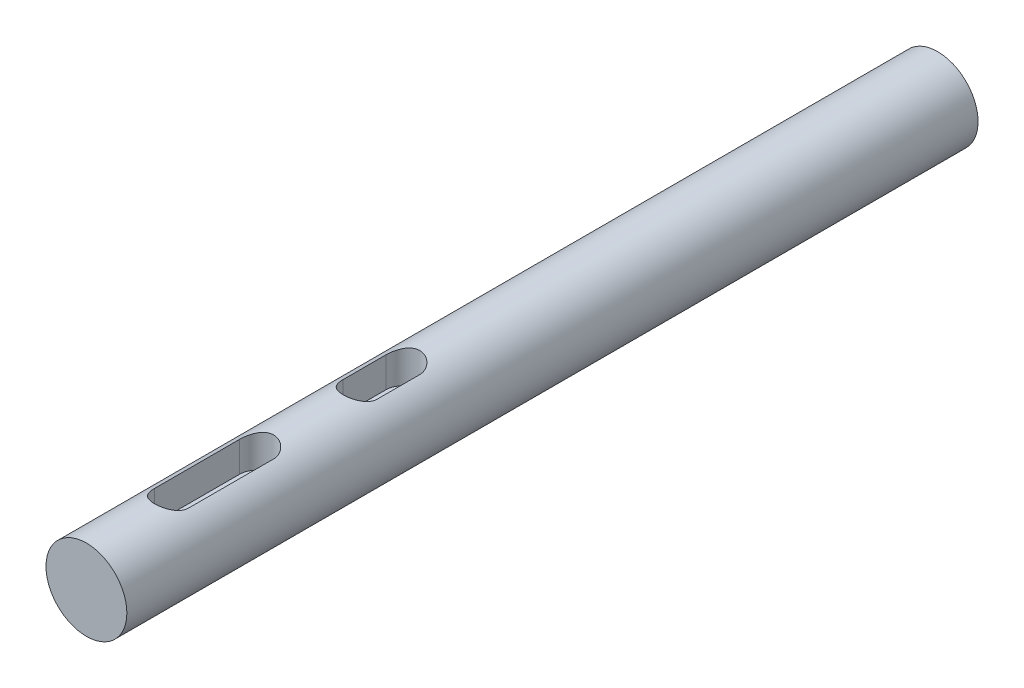
SolidWorks part; units mm, degrees
ref_plane "Front Plane" through (0, 0, 0) normal (0, 0, 1) x (1, 0, 0)
ref_plane "Top Plane" through (0, 0, 0) normal (0, 1, 0) x (1, 0, 0)
ref_plane "Right Plane" through (0, 0, 0) normal (1, 0, 0) x (0, 0, -1)
sketch "Sketch1" plane through (0, 0, 0) normal (0, 0, 1) x (1, 0, 0)
  circle A0 centre (0, 0) radius 4.75
  dimension "D1" = 9.5
extrude "Boss-Extrude1" add sketch "Sketch1" along normal blind 0.0001
sketch "Sketch4" plane through (0, 0, 0) normal (0, 0, -1) x (-1, 0, 0)
  circle A0 centre (0, 0) radius 4.75
  dimension "D1" = 9.5
extrude "Boss-Extrude2" add sketch "Sketch4" along normal blind 105
ref_axis "Axis1" through (0, 0, -105) along (0, 0, 1)
ref_plane "Plane1" through (0, 4.75, 0) normal (0, 1, 0) x (1, 0, 0)
sketch "Sketch5" plane through (0, 4.75, 0) normal (0, 1, 0) x (1, 0, 0)
  line L0 (0, -4.3175) -> (0, 99.6122) construction
  line L1 (0, 10) -> (0, 20) construction
  line L2 (-2, 10) -> (-2, 20)
  line L3 (2, 10) -> (2, 20)
  line L11 (0, 32.17) -> (0, 37.17) construction
  line L12 (-2, 32.17) -> (-2, 37.17)
  line L13 (2, 32.17) -> (2, 37.17)
  arc A0 (-2, 10) -> (2, 10) centre (0, 10) ccw
  arc A1 (2, 20) -> (-2, 20) centre (0, 20) ccw
  arc A6 (-2, 32.17) -> (2, 32.17) centre (0, 32.17) ccw
  arc A7 (2, 37.17) -> (-2, 37.17) centre (0, 37.17) ccw
  point P5 (0, 15)
  point P28 (0, 34.67)
  dimension "D1" = 10
  dimension "D2" = 4
  dimension "D3" = 12.17
  dimension "D11" = 2.5
  dimension "D12" = 4
extrude "Cut-Extrude3" cut sketch "Sketch5" against normal blind 4
sketch "Sketch6" plane through (0, 0, -105) normal (0, 0, -1) x (-1, 0, 0)
  circle A0 centre (0, 0) radius 4.75
extrude "Cut-Extrude4" cut sketch "Sketch6" against normal blind 5
